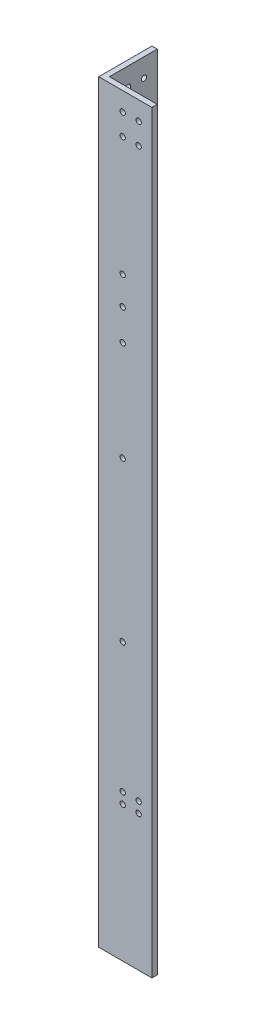
SolidWorks part; units mm, degrees
ref_plane "Front Plane" through (0, 0, 0) normal (0, 0, 1) x (1, 0, 0)
ref_plane "Top Plane" through (0, 0, 0) normal (0, 1, 0) x (1, 0, 0)
ref_plane "Right Plane" through (0, 0, 0) normal (1, 0, 0) x (0, 0, -1)
sketch "Sketch2" plane through (0, 0, 0) normal (0, 1, 0) x (1, 0, 0)
  line L0 (0, 31.75) -> (3.175, 31.75)
  line L1 (3.175, 31.75) -> (3.175, 3.175)
  line L2 (3.175, 3.175) -> (31.75, 3.175)
  line L3 (31.75, 3.175) -> (31.75, 0)
  line L4 (31.75, 0) -> (0, 0)
  line L5 (0, 0) -> (0, 31.75)
  point P9 (1.5875, 31.75)
  point P10 (31.75, 1.5875)
  dimension "D4" = 3.175
  dimension "D1" = 31.75
  dimension "D2" = 31.75
  dimension "D3" = 3.175
extrude "Boss-Extrude1" add sketch "Sketch2" along normal blind 450
sketch "FrontSideHoles-Sketch3" plane through (0, 0, 0) normal (0, 0, 1) x (1, 0, 0)
  line L0 (0, 0) -> (31.75, 0) construction
  line L3 (0, 450) -> (0, 0) construction
  circle A0 centre (14.2875, 81.1125) radius 1.5875
  circle A1 centre (23.8125, 81.1125) radius 1.5875
  circle A2 centre (14.2875, 87.4625) radius 1.5875
  circle A3 centre (23.8125, 87.4625) radius 1.5875
  circle A4 centre (14.2875, 438.8875) radius 1.5875
  circle A5 centre (14.2875, 426.1875) radius 1.5875
  circle A6 centre (23.8125, 438.8875) radius 1.5875
  circle A7 centre (23.8125, 426.1875) radius 1.5875
  circle A8 centre (14.2875, 338.1776) radius 1.5875
  circle A9 centre (14.2875, 319.6526) radius 1.5875
  circle A10 centre (14.2875, 260) radius 1.5875
  circle A11 centre (14.2875, 165) radius 1.5875
  circle A12 centre (14.2875, 355) radius 1.5875
  dimension "D4" = 3.175
  dimension "D1" = 81.1125
  dimension "D2" = 14.2875
  dimension "D8" = 11.1125
  dimension "D11" = 18.525
  dimension "D5" = 6.35
  dimension "D3" = 9.525
  dimension "D7" = 12.7
  dimension "D9" = 319.6526
  dimension "D6" = 165
  dimension "D10" = 95
  dimension "D13" = 95
sketch "LeftSideHoles-Sketch4" plane through (0, 0, 0) normal (-1, 0, 0) x (0, 0, 1)
  line L0 (-31.75, 450) -> (0, 450) construction
  line L1 (0, 450) -> (0, 0) construction
  line L3 (-31.75, 0) -> (0, 0) construction
  circle A0 centre (-23.8125, 81.1125) radius 1.5875
  circle A1 centre (-14.2875, 81.1125) radius 1.5875
  circle A2 centre (-23.8125, 87.4625) radius 1.5875
  circle A3 centre (-14.2875, 87.4625) radius 1.5875
  circle A4 centre (-23.8125, 438.8875) radius 1.5875
  circle A5 centre (-14.2875, 438.8875) radius 1.5875
  circle A6 centre (-23.8125, 426.1875) radius 1.5875
  circle A7 centre (-14.2875, 426.1875) radius 1.5875
  circle A8 centre (-23.8125, 332.6026) radius 1.5875
  circle A9 centre (-14.2875, 332.6026) radius 1.5875
  circle A10 centre (-23.8125, 319.9026) radius 1.5875
  circle A11 centre (-14.2875, 319.9026) radius 1.5875
  circle A12 centre (-23.8125, 7.9375) radius 1.5875
  circle A13 centre (-14.2875, 7.9375) radius 1.5875
  dimension "D4" = 3.175
  dimension "D2" = 14.2875
  dimension "D7" = 12.7
  dimension "D3" = 81.1125
  dimension "D6" = 11.1125
  dimension "D5" = 6.35
  dimension "D10" = 7.9375
  dimension "D9" = 12.7
  dimension "D11" = 9.525
  dimension "D8" = 332.6026
extrude "FrontSideHoles-Cut-Extrude1" cut sketch "FrontSideHoles-Sketch3" against normal blind 3.175
extrude "LeftSideHoles-Cut-Extrude2" cut sketch "LeftSideHoles-Sketch4" against normal blind 3.175
equation "\"RailThickness\"= .125in'Spec"
equation "\"VSWidth\"= 1.25in'Spec"
equation "\"VSHeight\"= 1.25in'Spec"
equation "\"VSLength\"= 450mm"
equation "\"HoleOffsetFromEdge\"= \"RailThickness\" * 2.5"
equation "\"HoleOffsetFromSide\"= \"RailThickness\" * 3.5"
equation "\"LegHeight\"= 70mm'Space needed for PSU/Stepper/Electronics"
equation "\"VSBottomSideRailHoleY1FromBottomOfLowerRail\"= \"V1 BottomOfLowerRail\" + \"HoleOffsetFromSide\"'Equals 70.1125"
equation "\"VSSideRailHoleX1FromSide\"= \"HoleOffsetFromSide\" + \"RailThickness\""
equation "\"FasteningHoleDiameter\"= .125in"
equation "\"VSBottomSideRailHoleY2FromY1\"= \"LowerRailHeight\" - \"HoleOffsetFromSide\" - \"HoleOffsetFromEdge\"'Equals 6.35"
equation "\"VSTopSideRailHoleY1FromEdge\"= \"HoleOffsetFromEdge\" + \"RailThickness\""
equation "\"D4@FrontSideHoles-Sketch3\" = \"FasteningHoleDiameter\""
equation "\"D1@FrontSideHoles-Sketch3\" = \"VSBottomSideRailHoleY1FromBottomOfLowerRail\""
equation "\"D2@FrontSideHoles-Sketch3\" = \"VSSideRailHoleX1FromSide\""
equation "\"D1@Boss-Extrude1\"=\"VSLength\""
equation "\"D4@LeftSideHoles-Sketch4\" = \"FasteningHoleDiameter\""
equation "\"D3@LeftSideHoles-Sketch4\"= \"VSBottomSideRailHoleY1FromBottomOfLowerRail\""
equation "\"D2@LeftSideHoles-Sketch4\" = \"VSSideRailHoleX1FromSide\""
equation "\"D8@FrontSideHoles-Sketch3\" = \"VSTopSideRailHoleY1FromEdge\""
equation "\"D6@LeftSideHoles-Sketch4\" = \"VSTopSideRailHoleY1FromEdge\""
equation "\"VSMidSideRailHoleY1FromV8TopOfMidSideRail\"= \"V8 ToTopOfMidSideRail\" - \"HoleOffsetFromEdge\"'Equals 308.2875"
equation "\"LowerRailHeight\"= 1.00in"
equation "\"D1@Sketch2\"=\"VSHeight\""
equation "\"D2@Sketch2\"=\"VSWidth\""
equation "\"TopRailHeight\"= 1.25in"
equation "\"MidSideRailHeight\"= 1.25in"
equation "\"D5@LeftSideHoles-Sketch4\"=\"VSBottomSideRailHoleY2FromY1\""
equation "\"D5@FrontSideHoles-Sketch3\"=\"VSBottomSideRailHoleY2FromY1\""
equation "\"D10@LeftSideHoles-Sketch4\"=\"HoleOffsetFromEdge\""
equation "\"VSMidSideRailHoleY2FromY1\"= \"MidSideRailHeight\" - \"HoleOffsetFromSide\" - \"HoleOffsetFromEdge\"'Equals 12.7"
equation "\"D9@LeftSideHoles-Sketch4\"=\"VSMidSideRailHoleY2FromY1\""
equation "\"VSSideRailHoleX2FromX1\"= \"VSWidth\" - \"VSSideRailHoleX1FromSide\" - \"HoleOffsetFromEdge\""
equation "\"D3@FrontSideHoles-Sketch3\"=\"VSSideRailHoleX2FromX1\""
equation "\"D7@FrontSideHoles-Sketch3\"=\"VSMidSideRailHoleY2FromY1\""
equation "\"D11@LeftSideHoles-Sketch4\"=\"VSSideRailHoleX2FromX1\""
equation "\"VSTopSideRailHoleY2FromY1\"= \"TopRailHeight\" - \"VSTopSideRailHoleY1FromEdge\" - \"HoleOffsetFromEdge\"'Equals 12.7"
equation "\"D7@LeftSideHoles-Sketch4\"=\"VSTopSideRailHoleY2FromY1\""
equation "\"BeltTensionerInnerHeight\"= \"20TGT2PulleyWidth\" * 2 + \"1mmSpacer\" * 3"
equation "\"20TGT2PulleyWidth\"= 8.7mm'The STL of the Pulley in the diagram is a bit larger"
equation "\"1mmSpacer\"= 1mm"
equation "\"BeltTensionerHeight\"= \"BeltTensionerInnerHeight\" + \"BeltTensionerUpperLowerWallThickness\" * 2"
equation "\"BeltTensionerUpperLowerWallThickness\"= 7mm"
equation "\"D11@FrontSideHoles-Sketch3\"=\"VSBeltTensionerHoleY2FromY1\""
equation "\"VSBeltTensionerHoleY1FromBottom\"= \"V9 FromBottomGantryPulleyToBottomOfBeltTensioner\" + \"HoleOffsetFromEdge\""
equation "\"VSBeltTensionerHoleY2FromY1\"= \"BeltTensionerHeight\" - \"HoleOffsetFromEdge\" * 2"
equation "\"V1 BottomOfLowerRail\"= \"LegHeight\""
equation "\"StepperShaftLength\"= 24mm'Pulley will be attached to the end"
equation "\"ZAxisLeadScrewLength\"= 200mm"
equation "\"LM8UUHeight\"= 24mm'Spec"
equation "\"V2 ToBedAtTopOfZAxis\"= \"V1 BottomOfLowerRail\" + \"StepperShaftLength\" + \"ZAxisLeadScrewLength\" - \"LM8UUHeight\" / 2"
equation "\"HotEndToTopOfXAxisGB\"= 63.315144mm'Measured from the100.Should be 63.315144"
equation "\"TopOfGBToBottomOfLinearRail\"= \"LinearGBWidth\" / 2 + \"LinearRailWidth\" / 2"
equation "\"LinearGBWidth\"= 27mm'Spec"
equation "\"V5 ToBottomOfXAxisLinearRail\"= \"V4 ToTopOfBuildPlate/HotEndTip\" + \"HotEndToTopOfXAxisGB\" - \"TopOfGBToBottomOfLinearRail\""
equation "\"LinearRailWidth\"= 12mm'Spec"
equation "\"V6 ToBottomOfGantryPulley\"= \"V5 ToBottomOfXAxisLinearRail\" - \"DistanceFromGABTopToLowerPulley\""
equation "\"GABUpperHeight\"= 6mm"
equation "\"GABMidWallHeight\"= 28mm'Must equal 28 or changes alignment"
equation "\"GABMidShortRiserHeight\"= \"GABMidWallHeight\" / 2 - \"20TGT2PulleyWidth\"'Equals 5.3"
equation "\"GABRiserBossOffset\"= 0.8mm'Aligns Pulleys"
equation "\"DistanceFromGABTopToLowerPulley\"= \"GABUpperHeight\" + \"GABMidWallHeight\" - \"GABMidShortRiserHeight\" + \"GABRiserBossOffset\" / 2"
equation "\"V7 ToTopOfMidBackRail\"= \"V6 ToBottomOfGantryPulley\" + \"StepperShaftLength\""
equation "\"D8@LeftSideHoles-Sketch4\"= \"VSMidSideRailHoleY1FromV8TopOfMidSideRail\""
equation "\"BedToBuildPlateStandoffLength\"= 15mm"
equation "\"BuildPlateHeight\"= 8mm'Spec"
equation "\"V4 ToTopOfBuildPlate/HotEndTip\"= \"V2 ToBedAtTopOfZAxis\" + \"BedToBuildPlateStandoffLength\" + \"BuildPlateHeight\""
equation "\"D9@FrontSideHoles-Sketch3\"=\"VSBeltTensionerHoleY1FromBottom\""
equation "\"V8 ToTopOfMidSideRail\"= \"V7 ToTopOfMidBackRail\" - \"RailThickness\""
equation "\"V9 FromBottomGantryPulleyToBottomOfBeltTensioner\"= \"V6 ToBottomOfGantryPulley\" - \"BeltTensionerUpperLowerWallThickness\" - \"1mmSpacer\""
equation "\"BeltTensionerMountingHoleOffsetFromEdge\"= \"HoleOffsetFromEdge\""
equation "\"VSBeltTensionerXMountingHoleOffsetFromSide\"= \"BeltTensionerMountingHoleOffsetFromEdge\" + \"RailThickness\" * 2"
equation "\"VSEnclosureOffsets\"= ( \"VSLength\" - \"LegHeight\" ) / 4"
equation "\"D6@FrontSideHoles-Sketch3\"=\"LegHeight\" + \"VSEnclosureOffsets\""
equation "\"D10@FrontSideHoles-Sketch3\"=\"VSEnclosureOffsets\""
equation "\"D13@FrontSideHoles-Sketch3\"=\"VSEnclosureOffsets\""
